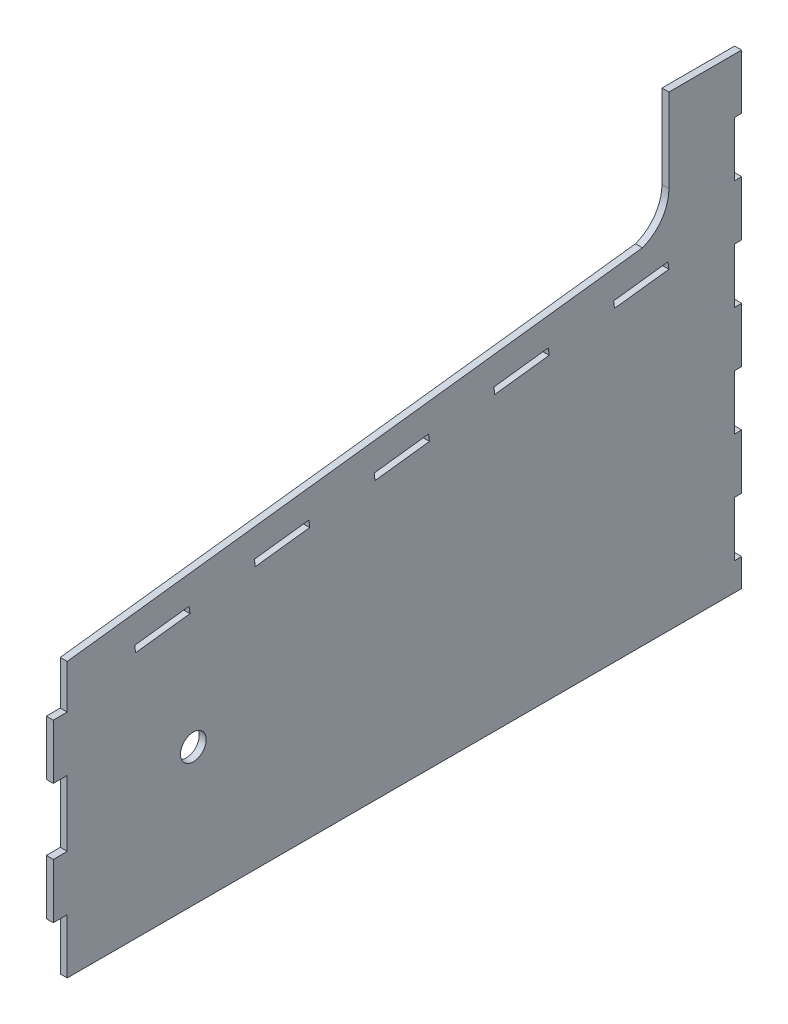
SolidWorks part; units mm, degrees
material "Beech"
ref_plane "Front Plane" through (0, 0, 0) normal (0, 0, 1) x (1, 0, 0)
ref_plane "Top Plane" through (0, 0, 0) normal (0, 1, 0) x (1, 0, 0)
ref_plane "Right Plane" through (0, 0, 0) normal (1, 0, 0) x (0, 0, -1)
sketch "Sketch1" plane through (0, 0, 0) normal (1, 0, 0) x (0, 0, -1)
  line L0 (0, 250) -> (524.53, 314.4042)
  line L1 (0, 0) -> (615, 0)
  line L2 (0, 0) -> (0, 50)
  line L7 (615, 425.32) -> (548.65, 425.32)
  line L8 (548.65, 349.09) -> (548.65, 425.32)
  line L9 (0, 250) -> (615, 250) construction
  line L10 (524.53, 314.4042) -> (615, 325.5125) construction
  line L11 (-12.7, 160) -> (-12.7, 210)
  line L12 (0, 50) -> (-12.7, 50)
  line L14 (0, 100) -> (-12.7, 100)
  line L15 (-12.7, 50) -> (-12.7, 100)
  line L16 (0, 160) -> (-12.7, 160)
  line L18 (0, 210) -> (-12.7, 210)
  line L19 (0, 210) -> (0, 250)
  line L21 (0, 100) -> (0, 160)
  line L40 (615, 425.32) -> (615, 0)
  arc A0 (524.53, 314.4042) -> (548.65, 349.09) centre (511.65, 349.09) ccw
  dimension "D4" = 37
  dimension "D1" = 615
  dimension "D2" = 250
  dimension "D3" = 66.35
  dimension "D5" = 7
  dimension "D6" = 175.32
  dimension "D7" = 76.23
  dimension "D8" = 12.7
  dimension "D9" = 50
  dimension "D10" = 50
  dimension "D11" = 2
  dimension "D12" = 40
extrude "Boss-Extrude1" add sketch "Sketch1" along normal blind 6.35
sketch "Sketch2" plane through (6.35, 0, 0) normal (1, 0, 0) x (0, 0, -1)
  line L0 (524.53, 314.4042) -> (615, 325.5125) construction
  line L2 (524.53, 314.4042) -> (0, 250) construction
  line L3 (0, 224.4093) -> (615, 299.9218) construction
  line L4 (0, 50) -> (0, 0) construction
  line L5 (61.5379, 231.9651) -> (62.3117, 225.6625)
  line L6 (62.3117, 225.6625) -> (111.939, 231.7559)
  line L7 (111.939, 231.7559) -> (111.1652, 238.0586)
  line L8 (111.1652, 238.0586) -> (61.5379, 231.9651)
  line L9 (220.3452, 251.4642) -> (170.7179, 245.3708)
  line L10 (170.7179, 245.3708) -> (171.4918, 239.0681)
  line L11 (171.4918, 239.0681) -> (221.1191, 245.1616)
  line L12 (221.1191, 245.1616) -> (220.3452, 251.4642)
  line L13 (329.5253, 264.8699) -> (279.898, 258.7764)
  line L14 (279.898, 258.7764) -> (280.6719, 252.4737)
  line L15 (280.6719, 252.4737) -> (330.2992, 258.5672)
  line L16 (330.2992, 258.5672) -> (329.5253, 264.8699)
  line L17 (438.7054, 278.2755) -> (389.0781, 272.182)
  line L18 (389.0781, 272.182) -> (389.852, 265.8794)
  line L19 (389.852, 265.8794) -> (439.4793, 271.9728)
  line L20 (439.4793, 271.9728) -> (438.7054, 278.2755)
  line L21 (547.8855, 291.6811) -> (498.2582, 285.5877)
  line L22 (498.2582, 285.5877) -> (499.032, 279.285)
  line L23 (499.032, 279.285) -> (548.6593, 285.3785)
  line L24 (548.6593, 285.3785) -> (547.8855, 291.6811)
  line L25 (0, 160) -> (0, 100) construction
  line L26 (0, 0) -> (615, 0) construction
  line L27 (615, 0) -> (615, 425.32) construction
  line L28 (615, 375.32) -> (608.65, 375.32)
  line L29 (615, 375.32) -> (615, 325.32)
  line L30 (615, 325.32) -> (608.65, 325.32)
  line L31 (608.65, 375.32) -> (608.65, 325.32)
  line L32 (615, 425.32) -> (548.65, 425.32) construction
  line L45 (615, 275.32) -> (615, 225.32)
  line L46 (615, 275.32) -> (608.65, 275.32)
  line L47 (608.65, 275.32) -> (608.65, 225.32)
  line L48 (615, 225.32) -> (608.65, 225.32)
  line L49 (615, 175.32) -> (615, 125.32)
  line L50 (615, 175.32) -> (608.65, 175.32)
  line L51 (608.65, 175.32) -> (608.65, 125.32)
  line L52 (615, 125.32) -> (608.65, 125.32)
  line L53 (615, 75.32) -> (615, 25.32)
  line L54 (615, 75.32) -> (608.65, 75.32)
  line L55 (608.65, 75.32) -> (608.65, 25.32)
  line L56 (615, 25.32) -> (608.65, 25.32)
  circle A0 centre (115, 125) radius 11.735
  dimension "D5" = 23.47
  dimension "D1" = 25.4
  dimension "D2" = 50
  dimension "D3" = 6.35
  dimension "D4" = 62
  dimension "D6" = 115
  dimension "D7" = 125
  dimension "D8" = 6.35
  dimension "D9" = 50
  dimension "D10" = 50
extrude "Cut-Extrude1" cut sketch "Sketch2" against normal blind 6.35
